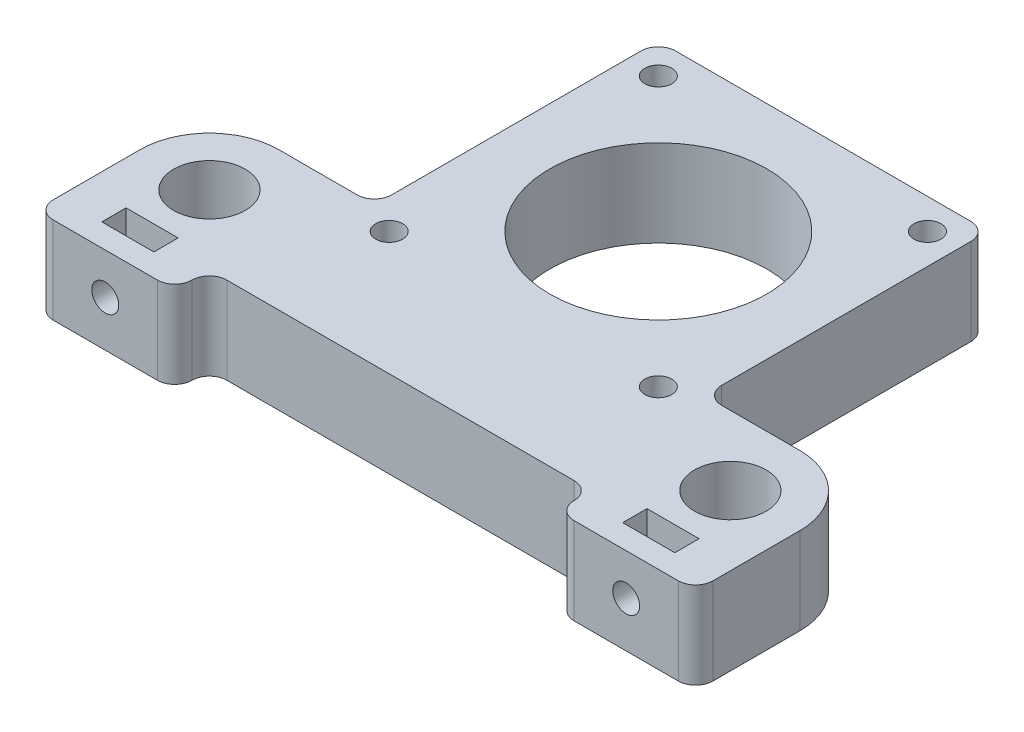
SolidWorks part; units mm, degrees
ref_plane "Front Plane" through (0, 0, 0) normal (0, 0, 1) x (1, 0, 0)
ref_plane "Top Plane" through (0, 0, 0) normal (0, 1, 0) x (1, 0, 0)
ref_plane "Right Plane" through (0, 0, 0) normal (1, 0, 0) x (0, 0, -1)
sketch "Sketch1" plane through (0, 0, 0) normal (0, 1, 0) x (1, 0, 0)
  line L0 (0, 8) -> (0, -8) construction
  line L1 (-38, 8) -> (38, 8)
  line L2 (-38, 8) -> (-38, -8)
  line L3 (-38, -8) -> (38, -8)
  line L4 (38, 8) -> (38, -8)
  line L5 (-38, 8) -> (38, -8) construction
  line L6 (-38, -8) -> (38, 8) construction
  line L7 (-38, -8) -> (-22, -8)
  line L8 (-38, -8) -> (-38, -12)
  line L9 (-38, -12) -> (-22, -12)
  line L10 (-22, -8) -> (-22, -12)
  line L11 (22, -8) -> (22, -12)
  line L12 (38, -12) -> (22, -12)
  line L13 (38, -8) -> (38, -12)
  circle A0 centre (-30, 0) radius 4.125
  circle A1 centre (30, 0) radius 4.125
  point P4 (0, 0)
  dimension "D1" = 8.25
  dimension "D2" = 60
  dimension "D3" = 30
  dimension "D4" = 8
  dimension "D5" = 8
  dimension "D6" = 8
  dimension "D7" = 8
  dimension "D8" = 16
  dimension "D9" = 4
extrude "Boss-Extrude1" add sketch "Sketch1" along normal blind 10 contours L10 L3 L8 L9 | L4 L1 L2 L3 A1 A0 | L13 L3 L11 L12 region at (0, 0, 0) region at (-30, 0, 10) region at (30, 0, 10)
sketch "Sketch2" plane through (0, 10, 0) normal (0, 1, 0) x (1, 0, 0)
  line L1 (-33, -6.6) -> (-27, -6.6)
  line L2 (-33, -6.6) -> (-33, -9.4)
  line L3 (-33, -9.4) -> (-27, -9.4)
  line L4 (-27, -6.6) -> (-27, -9.4)
  line L5 (-33, -6.6) -> (-27, -9.4) construction
  line L6 (-33, -9.4) -> (-27, -6.6) construction
  point P0 (-30, -8)
  point P7 (-30, 0)
  dimension "D1" = 2.8
  dimension "D2" = 6
  dimension "D3" = 8
extrude "Cut-Extrude1" cut sketch "Sketch2" against normal blind 10
sketch "Sketch3" plane through (0, 0, 12) normal (0, 0, 1) x (1, 0, 0)
  circle A0 centre (-30, 5.2586) radius 1.55
  dimension "D1" = 3.1
extrude "Cut-Extrude2" cut sketch "Sketch3" against normal blind 10
mirror "Mirror1" about plane through (0, 0, 0) normal (1, 0, 0) of "Cut-Extrude1", "Cut-Extrude2"
fillet "Fillet1" radius 8 2 edges at (38, 5, -8) (-38, 5, -8)
fillet "Fillet2" radius 2 6 edges at (38, 5, 12) (22, 5, 12) (22, 5, 8) (-22, 5, 8) (-22, 5, 12) (-38, 5, 12)
sketch "Sketch4" plane through (0, 0, 0) normal (0, -1, 0) x (1, 0, 0)
  line L1 (-15.5, -6.2) -> (15.5, -6.2)
  line L2 (-15.5, -6.2) -> (-15.5, -37.2)
  line L3 (-15.5, -37.2) -> (15.5, -37.2)
  line L4 (15.5, -6.2) -> (15.5, -37.2)
  line L5 (-15.5, -6.2) -> (15.5, -37.2) construction
  line L6 (-15.5, -37.2) -> (15.5, -6.2) construction
  line L7 (-19, -2.7) -> (19, -2.7)
  line L8 (-19, -2.7) -> (-19, -40.7)
  line L9 (-19, -40.7) -> (19, -40.7)
  line L10 (19, -2.7) -> (19, -40.7)
  line L11 (-19, -2.7) -> (19, -40.7) construction
  line L12 (-19, -40.7) -> (19, -2.7) construction
  circle A0 centre (0, -21.7) radius 12.5
  circle A1 centre (-30, 0) radius 4.125 construction
  circle A2 centre (-15.5, -6.2) radius 1.55
  circle A3 centre (15.5, -6.2) radius 1.55
  circle A4 centre (15.5, -37.2) radius 1.55
  circle A5 centre (-15.5, -37.2) radius 1.55
  line M8 (20, 8) -> (-20, 8)
  dimension "D1" = 25
  dimension "D5" = 3.1
  dimension "D2" = 21.7
  dimension "D3" = 31
  dimension "D4" = 31
  dimension "D6" = 3.5
  dimension "D7" = 3.5
extrude "Boss-Extrude2" add sketch "Sketch4" against normal blind 10 contours A3 L4 L10 L7 L8 L2 A2 L1 M8 | A3 L1 A2 L2 L4 A0 M8 | A5 L3 A4 L4 L2 M8 | A5 L2 L8 L9 L10 L4 A4 L3 M8 region at (0, 0, -6.6384) region at (0, 0, -3.2374)
extrude "Cut-Extrude3" cut sketch "Sketch4<3>" against normal blind 10 contours L4 A3 L1 | L1 A3 L4 | L1 A2 L2 | L2 A2 L1 region at (-15.7193, 0, -5.9807) region at (-14.8422, 0, -6.8578) region at (15.7193, 0, -5.9807) region at (14.8422, 0, -6.8578)
sketch "Sketch4<3>" plane through (0, 0, 0) normal (0, -1, 0) x (1, 0, 0) same geometry as "Sketch4"
fillet "Fillet4" radius 2 4 edges at (-19, 5, -40.7) (19, 5, -40.7) (19, 5, -8) (-19, 5, -8)
